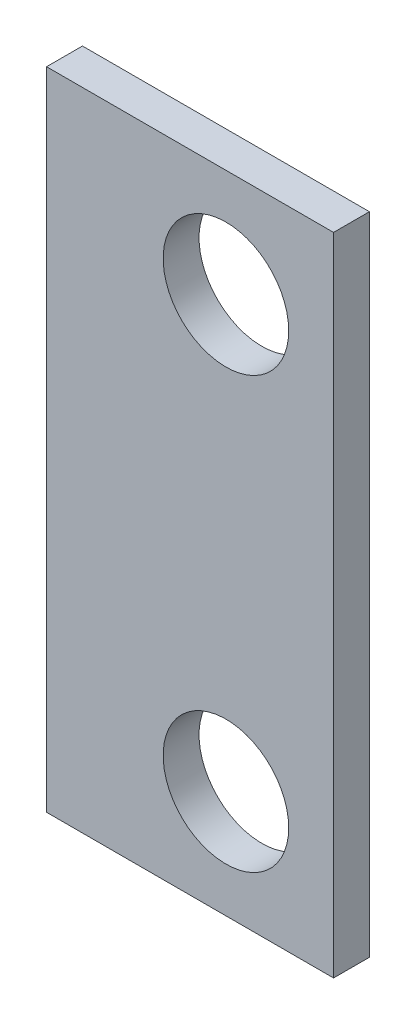
SolidWorks part; units mm, degrees
ref_plane "Front Plane" through (0, 0, 0) normal (0, 0, 1) x (1, 0, 0)
ref_plane "Top Plane" through (0, 0, 0) normal (0, 1, 0) x (1, 0, 0)
ref_plane "Right Plane" through (0, 0, 0) normal (1, 0, 0) x (0, 0, -1)
sketch "Sketch1" plane through (0, 0, 0) normal (0, 1, 0) x (1, 0, 0)
  line L1 (0, 0) -> (50.8, 0)
  line L2 (0, 0) -> (0, 6.35)
  line L3 (0, 6.35) -> (50.8, 6.35)
  line L4 (50.8, 0) -> (50.8, 6.35)
  dimension "D1" = 50.8
  dimension "D2" = 6.35
extrude "Boss-Extrude1" add sketch "Sketch1" along normal blind 114.3
sketch "Sketch2" plane through (0, 0, 0) normal (0, 0, 1) x (1, 0, 0)
  line L0 (31.75, 114.3) -> (31.75, -19.4121) construction
  line L1 (0, 114.3) -> (50.8, 114.3) construction
  line L2 (50.8, 114.3) -> (50.8, 0) construction
  line L3 (31.75, 95.25) -> (79.9301, 95.25) construction
  line L5 (31.75, 19.05) -> (82.1922, 19.05) construction
  line L6 (0, 0) -> (50.8, 0) construction
  circle A0 centre (31.75, 19.05) radius 11.1125
  circle A1 centre (31.75, 95.25) radius 11.1125
  dimension "D4" = 22.225
  dimension "D5" = 22.225
  dimension "D1" = 19.05
  dimension "D2" = 19.05
  dimension "D3" = 19.05
extrude "Cut-Extrude1" cut sketch "Sketch2" against normal through all
